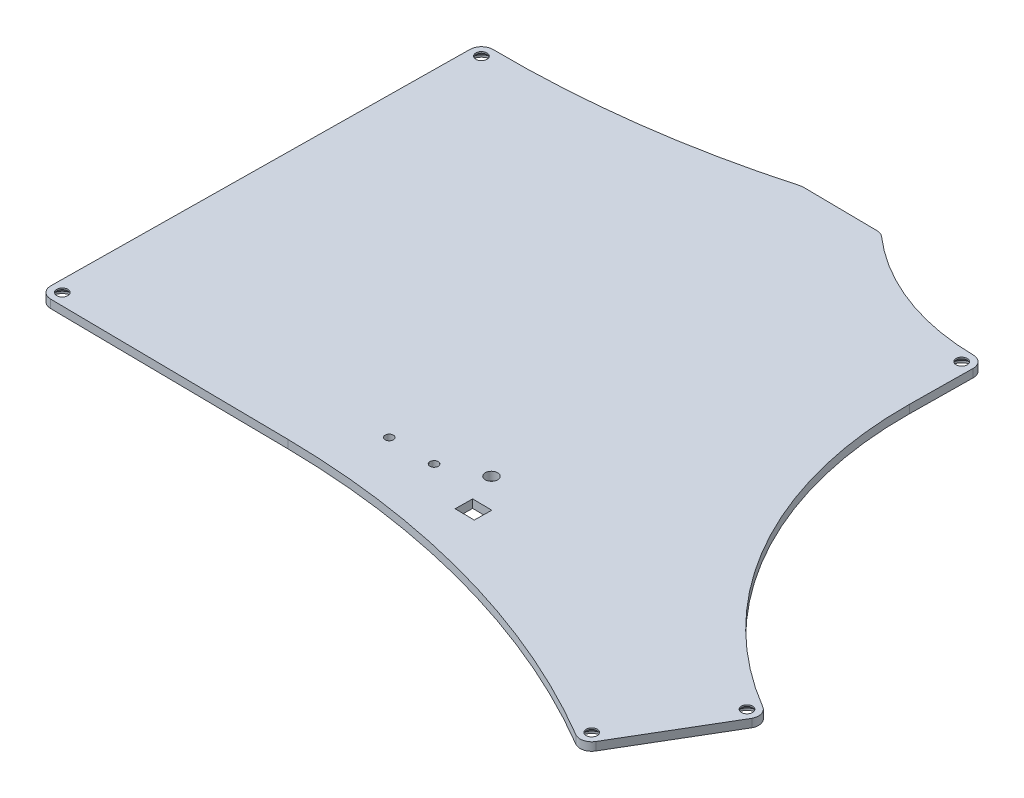
SolidWorks part; units mm, degrees
ref_plane "Front Plane" through (0, 0, 0) normal (0, 0, 1) x (1, 0, 0)
ref_plane "Top Plane" through (0, 0, 0) normal (0, 1, 0) x (1, 0, 0)
ref_plane "Right Plane" through (0, 0, 0) normal (1, 0, 0) x (0, 0, -1)
sketch "Main" plane through (0, 0, 0) normal (0, 1, 0) x (1, 0, 0)
  line L13 (-13.8307, -87.7787) -> (-9.531, -87.8292) construction
  line L18 (-14.0296, -87.6764) -> (-9.3299, -87.7315) construction
  line L19 (-14.0296, -87.6764) -> (-14.0788, -91.8761) construction
  line L20 (-9.3299, -87.7315) -> (-9.3791, -91.9312) construction
  line L21 (-14.0788, -91.8761) -> (-9.3791, -91.9312) construction
  line L22 (-13.9765, -91.6773) -> (-13.9319, -87.8776) construction
  line L23 (-9.4322, -87.9303) -> (-9.4768, -91.7301) construction
  line L26 (-9.578, -91.8289) -> (-13.8777, -91.7785) construction
  line L69 (-108.9821, 6.4438) -> (-110.1609, -94.0493)
  line L70 (-21.3415, 17.9166) -> (-39.3403, 18.1277)
  line L71 (19.277, -14.8479) -> (19.4562, 0.4369)
  line L72 (52.0453, -123.8081) -> (66.1172, -99.9838)
  line L73 (-107.1963, -97.0843) -> (-48.9877, -97.7671)
  line L74 (-108.9821, 6.4438) -> (-110.1609, -94.0493) construction
  line L75 (-21.3415, 17.9166) -> (-39.3403, 18.1277) construction
  line L76 (19.277, -14.8479) -> (19.4562, 0.4369) construction
  line L77 (52.0453, -123.8081) -> (66.1172, -99.9838) construction
  line L78 (-107.1963, -97.0843) -> (-48.9877, -97.7671) construction
  circle A0 centre (-107.1611, -94.0845) radius 1.35 construction
  circle A1 centre (-105.9823, 6.4086) radius 1.35 construction
  circle A2 centre (16.4564, 0.4721) radius 1.35 construction
  circle A3 centre (63.4478, -98.6043) radius 1.35 construction
  circle A4 centre (49.4623, -122.2824) radius 1.35 construction
  circle A11 centre (-16.4973, -80.647) radius 1.5 construction
  circle A19 centre (-16.4973, -80.647) radius 1.5 construction
  circle A83 centre (-105.9823, 6.4086) radius 1.35 construction
  circle A84 centre (16.4564, 0.4721) radius 1.35 construction
  circle A85 centre (63.4478, -98.6043) radius 1.35 construction
  circle A86 centre (49.4623, -122.2824) radius 1.35 construction
  circle A87 centre (-107.1611, -94.0845) radius 1.35 construction
  circle A125 centre (-26.0492, -85.0152) radius 1 construction
  circle A126 centre (-37.0484, -84.8862) radius 1 construction
  arc A135 (-110.1609, -94.0493) -> (-107.1963, -97.0843) centre (-107.1611, -94.0845) ccw
  arc A136 (-105.9472, 9.4084) -> (-108.9821, 6.4438) centre (-105.9823, 6.4086) ccw
  arc A137 (-105.9472, 9.4084) -> (-40.1817, 18.0176) centre (-103.1967, 243.8923) ccw
  arc A138 (-39.3403, 18.1277) -> (-40.1817, 18.0176) centre (-39.3755, 15.128) ccw
  arc A139 (-19.4037, 17.1768) -> (-21.3415, 17.9166) centre (-21.3767, 14.9168) ccw
  arc A140 (-19.4037, 17.1768) -> (16.4916, 3.4719) centre (17.1434, 59.0395) ccw
  arc A141 (19.4562, 0.4369) -> (16.4916, 3.4719) centre (16.4564, 0.4721) ccw
  arc A142 (19.277, -14.8479) -> (64.9759, -96.0171) centre (112.2741, -15.9387) ccw
  arc A143 (66.1172, -99.9838) -> (64.9759, -96.0171) centre (63.4478, -98.6043) ccw
  arc A144 (47.9366, -124.8655) -> (52.0453, -123.8081) centre (49.4623, -122.2824) ccw
  arc A145 (47.9366, -124.8655) -> (-48.9877, -97.7671) centre (-51.2758, -292.8371) ccw
  arc A146 (-110.1609, -94.0493) -> (-107.1963, -97.0843) centre (-107.1611, -94.0845) ccw construction
  arc A147 (-105.9472, 9.4084) -> (-108.9821, 6.4438) centre (-105.9823, 6.4086) ccw construction
  arc A148 (-105.9472, 9.4084) -> (-40.1817, 18.0176) centre (-103.1967, 243.8923) ccw construction
  arc A149 (-39.3403, 18.1277) -> (-40.1817, 18.0176) centre (-39.3755, 15.128) ccw construction
  arc A150 (-19.4037, 17.1768) -> (-21.3415, 17.9166) centre (-21.3767, 14.9168) ccw construction
  arc A151 (-19.4037, 17.1768) -> (16.4916, 3.4719) centre (17.1434, 59.0395) ccw construction
  arc A152 (19.4562, 0.4369) -> (16.4916, 3.4719) centre (16.4564, 0.4721) ccw construction
  arc A153 (19.277, -14.8479) -> (64.9759, -96.0171) centre (112.2741, -15.9387) ccw construction
  arc A154 (66.1172, -99.9838) -> (64.9759, -96.0171) centre (63.4478, -98.6043) ccw construction
  arc A155 (47.9366, -124.8655) -> (52.0453, -123.8081) centre (49.4623, -122.2824) ccw construction
  arc A156 (47.9366, -124.8655) -> (-48.9877, -97.7671) centre (-51.2758, -292.8371) ccw construction
  dimension "D2" = 3
  dimension "D3" = 2
  dimension "D4" = 0.1
  dimension "D5" = 0.1
  dimension "D6" = 0.1
  dimension "D7" = 0.1
  dimension "D1" = 0
sketch "Sketch7" plane through (0, 0, 0) normal (0, 1, 0) x (1, 0, 0)
  line L0 (-14.0296, -87.6764) -> (-9.3299, -87.7315)
  line L1 (-9.3299, -87.7315) -> (-9.3791, -91.9312)
  line L2 (-9.3791, -91.9312) -> (-14.0788, -91.8761)
  line L3 (-14.0788, -91.8761) -> (-14.0296, -87.6764)
  line L42 (-108.7822, 6.4414) -> (-109.9609, -94.0516)
  line L43 (-107.194, -96.8843) -> (-48.9853, -97.5671)
  line L44 (51.8731, -123.7064) -> (65.942, -99.887)
  line L45 (19.077, -14.8455) -> (19.2563, 0.4392)
  line L46 (-21.3439, 17.7166) -> (-39.3427, 17.9278)
  line L47 (-108.7822, 6.4414) -> (-109.9609, -94.0516)
  line L48 (-107.194, -96.8843) -> (-48.9853, -97.5671)
  line L49 (51.8731, -123.7064) -> (65.942, -99.887)
  line L50 (19.077, -14.8455) -> (19.2563, 0.4392)
  line L51 (-21.3439, 17.7166) -> (-39.3427, 17.9278)
  circle A0 centre (-37.0484, -84.8862) radius 1
  circle A1 centre (-26.0492, -85.0152) radius 1
  circle A2 centre (-16.4973, -80.647) radius 1.5
  circle A3 centre (-37.0484, -84.8862) radius 1 construction
  circle A4 centre (-16.4973, -80.647) radius 1.5 construction
  circle A99 centre (-105.9823, 6.4086) radius 1.35
  circle A100 centre (16.4564, 0.4721) radius 1.35
  circle A101 centre (63.4478, -98.6043) radius 1.35
  circle A102 centre (49.4623, -122.2824) radius 1.35
  circle A103 centre (-107.1611, -94.0845) radius 1.35
  circle A104 centre (-107.1611, -94.0845) radius 1.35 construction
  arc A110 (-105.9495, 9.2084) -> (-108.7822, 6.4414) centre (-105.9823, 6.4086) ccw
  arc A111 (-109.9609, -94.0516) -> (-107.194, -96.8843) centre (-107.1611, -94.0845) ccw
  arc A112 (48.0383, -124.6933) -> (-48.9853, -97.5671) centre (-51.2758, -292.8371) ccw
  arc A113 (48.0383, -124.6933) -> (51.8731, -123.7064) centre (49.4623, -122.2824) ccw
  arc A114 (65.942, -99.887) -> (64.8742, -96.1893) centre (63.4478, -98.6043) ccw
  arc A115 (19.077, -14.8455) -> (64.8742, -96.1893) centre (112.2741, -15.9387) ccw
  arc A116 (19.2563, 0.4392) -> (16.4893, 3.2719) centre (16.4564, 0.4721) ccw
  arc A117 (-19.5353, 17.0261) -> (16.4893, 3.2719) centre (17.1434, 59.0395) ccw
  arc A118 (-19.5353, 17.0261) -> (-21.3439, 17.7166) centre (-21.3767, 14.9168) ccw
  arc A119 (-39.3427, 17.9278) -> (-40.1279, 17.825) centre (-39.3755, 15.128) ccw
  arc A120 (-105.9495, 9.2084) -> (-40.1279, 17.825) centre (-103.1967, 243.8923) ccw
  arc A121 (-105.9495, 9.2084) -> (-108.7822, 6.4414) centre (-105.9823, 6.4086) ccw
  arc A122 (-109.9609, -94.0516) -> (-107.194, -96.8843) centre (-107.1611, -94.0845) ccw
  arc A123 (48.0383, -124.6933) -> (-48.9853, -97.5671) centre (-51.2758, -292.8371) ccw
  arc A124 (48.0383, -124.6933) -> (51.8731, -123.7064) centre (49.4623, -122.2824) ccw
  arc A125 (65.942, -99.887) -> (64.8742, -96.1893) centre (63.4478, -98.6043) ccw
  arc A126 (19.077, -14.8455) -> (64.8742, -96.1893) centre (112.2741, -15.9387) ccw
  arc A127 (19.2563, 0.4392) -> (16.4893, 3.2719) centre (16.4564, 0.4721) ccw
  arc A128 (-19.5353, 17.0261) -> (16.4893, 3.2719) centre (17.1434, 59.0395) ccw
  arc A129 (-19.5353, 17.0261) -> (-21.3439, 17.7166) centre (-21.3767, 14.9168) ccw
  arc A130 (-39.3427, 17.9278) -> (-40.1279, 17.825) centre (-39.3755, 15.128) ccw
  arc A131 (-105.9495, 9.2084) -> (-40.1279, 17.825) centre (-103.1967, 243.8923) ccw
  dimension "D1" = 0.2
extrude "Main_plate" add sketch "Sketch7" against normal blind 2
sketch "Sketch8" plane through (0, -2, 0) normal (0, 1, 0) x (1, 0, 0)
  circle A0 centre (-105.9823, 6.4086) radius 2.5
  circle A1 centre (16.4564, 0.4721) radius 2.5
  circle A2 centre (63.4478, -98.6043) radius 2.5
  circle A3 centre (49.4623, -122.2824) radius 2.5
  circle A4 centre (-107.1611, -94.0845) radius 2.5
  dimension "D1" = 5
extrude "Screw_holes" cut sketch "Sketch8" along normal blind 1.7
chamfer "Chamfer1" distance 1.2 angle 45 5 edges at (-107.1611, -0.3, 96.5845) (49.4623, -0.3, 124.7824) (63.4478, -0.3, 101.1043) (16.4564, -0.3, 2.0279) (-105.9823, -0.3, -3.9086)
